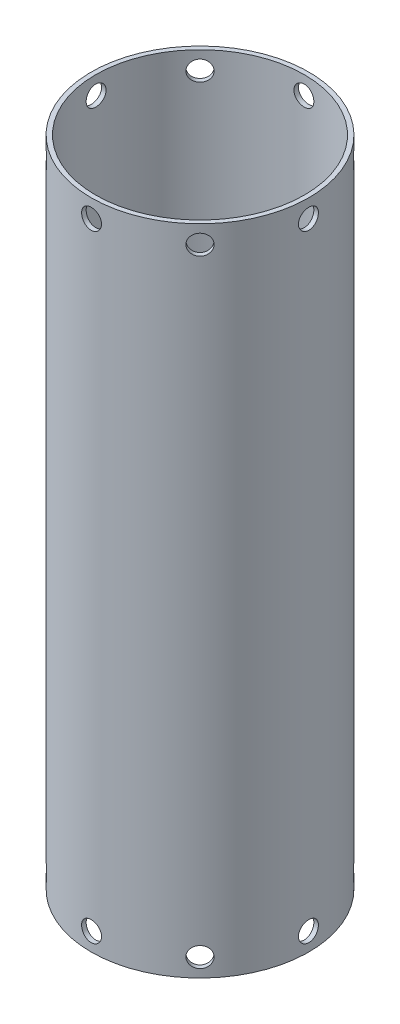
SolidWorks part; units mm, degrees
material "6061-T6 (SS)"
ref_plane "Front Plane" through (0, 0, 0) normal (0, 0, 1) x (1, 0, 0)
ref_plane "Top Plane" through (0, 0, 0) normal (0, 1, 0) x (1, 0, 0)
ref_plane "Right Plane" through (0, 0, 0) normal (1, 0, 0) x (0, 0, -1)
sketch "Sketch1" plane through (0, 0, 0) normal (0, 1, 0) x (1, 0, 0)
  circle A0 centre (0, 0) radius 76.2
  circle A1 centre (0, 0) radius 73.025
  dimension "D1" = 152.4
  dimension "D2" = 3.175
extrude "Boss-Extrude1" add sketch "Sketch1" along normal blind 457.2
sketch "Sketch2" [suppressed] plane through (0, 736.6, 0) normal (1, 0, 0) x (0, 0, 1)
  circle A0 centre (0, -12.7) radius 5.715 construction
  circle A1 centre (0, -12.7) radius 5.715 construction
  circle A2 centre (0, -12.7) radius 6.985
  dimension "D1" = 1.27
extrude "LOX Top Holes" [suppressed] cut sketch "Sketch2" along normal up to surface (75.8792 mm away) contours A2 up to face at (0, 457.2, 76.2)
pattern_circular "CirPattern1" [suppressed] count 8 over 360 of bodies 122
sketch "Sketch3" [suppressed] plane through (0, 25.4, 0) normal (1, 0, 0) x (0, 0, -1)
  circle A0 centre (0, -12.7) radius 5.715 construction
  circle A1 centre (0, -12.7) radius 5.715 construction
  circle A2 centre (0, -12.7) radius 6.985
  dimension "D1" = 1.27
extrude "LOX Bottom Holes" [suppressed] cut sketch "Sketch3" along normal up to surface (75.8792 mm away) contours A2 up to face at (0, 457.2, 76.2)
pattern_circular "CirPattern2" [suppressed] count 8 over 360 of bodies 124
sketch "Sketch4" plane through (0, 431.8, 0) normal (1, 0, 0) x (0, 0, 1)
  circle A0 centre (0, -12.7) radius 5.715 construction
  circle A1 centre (0, -12.7) radius 5.715 construction
  circle A2 centre (0, -12.7) radius 6.985
  dimension "D1" = 1.27
extrude "Cut-Extrude1" cut sketch "Sketch4" along normal up to surface (75.8792 mm away) contours A2 region at (0, 444.5, 0) up to face at (0, 457.2, 76.2)
pattern_circular "CirPattern3" count 8 over 360 about axis through (0, 457.2, 0) along (0, 1, 0) of "Cut-Extrude1"
sketch "Sketch7" plane through (0, 25.4, 0) normal (1, 0, 0) x (0, 0, -1)
  circle A0 centre (0, -12.7) radius 5.715 construction
  circle A1 centre (0, -12.7) radius 5.715 construction
  circle A2 centre (0, -12.7) radius 6.985
  dimension "D1" = 1.27
extrude "Cut-Extrude2" cut sketch "Sketch7" along normal up to surface (75.8792 mm away) up to face at (0, 457.2, 76.2)
pattern_circular "CirPattern4" count 8 over 360 about axis through (0, 0, 0) along (0, 1, 0) of "Cut-Extrude2"
